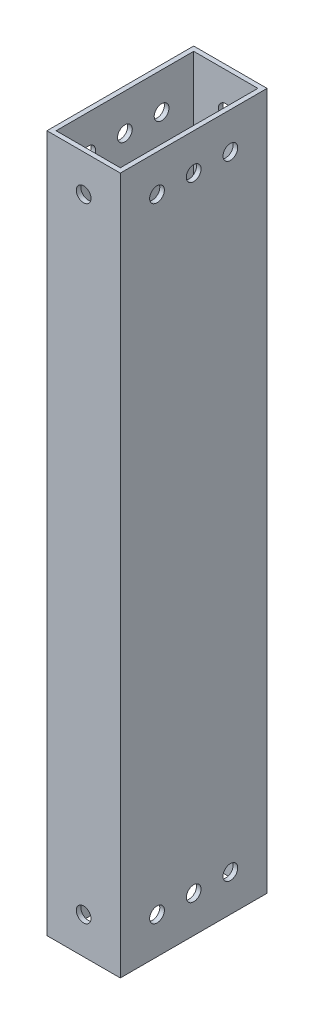
SolidWorks part; units mm, degrees
material "6061-T6 (SS)"
ref_plane "Front" through (0, 0, 0) normal (0, 0, 1) x (1, 0, 0)
ref_plane "Top" through (0, 0, 0) normal (0, 1, 0) x (1, 0, 0)
ref_plane "Right" through (0, 0, 0) normal (1, 0, 0) x (0, 0, -1)
sketch "Sketch1" plane through (0, 0, 0) normal (0, 1, 0) x (1, 0, 0)
  line L1 (12.7, 25.4) -> (-12.7, 25.4)
  line L2 (12.7, 25.4) -> (12.7, -25.4)
  line L3 (12.7, -25.4) -> (-12.7, -25.4)
  line L4 (-12.7, 25.4) -> (-12.7, -25.4)
  line L5 (12.7, 25.4) -> (-12.7, -25.4) construction
  line L6 (12.7, -25.4) -> (-12.7, 25.4) construction
  point P0 (0, 0)
  dimension "D1" = 25.4
  dimension "D2" = 50.8
extrude "Extrude-Thin1" add sketch "Sketch1" along normal up to surface (241.3 mm away) thin thin type one direction reverse wall 1.5875
sketch "Sketch4" plane through (-12.7, 0, 0) normal (-1, 0, 0) x (0, 0, 1)
  line L0 (-12.7, 12.7) -> (12.7, 12.7) construction
  line L3 (-12.7, 228.6) -> (12.7, 228.6) construction
  line L4 (-25.4, 0) -> (25.4, 0) construction
  line L5 (-25.4, 241.3) -> (25.4, 241.3) construction
  line L6 (-25.4, 241.3) -> (-25.4, 0) construction
  point P1 (-12.7, 12.7)
  point P2 (12.7, 12.7)
  point P6 (-12.7, 228.6)
  point P7 (12.7, 228.6)
  point P10 (0, 228.6)
  point P16 (-12.7, 228.6)
  point P18 (12.7, 228.6)
  point P22 (0, 12.7)
  point P26 (12.7, 12.7)
  point P28 (-12.7, 12.7)
  dimension "D1" = 12.7
  dimension "D2" = 12.7
  dimension "D3" = 12.7
hole_wizard "#10 Clearance Hole1" positions "Sketch4" profile "Sketch3" hole size "#10" standard "ANSI Inch" end condition through all
sketch "Sketch3" plane through (-12.7, 12.7, -12.7) normal (0, 1, 0) x (0, 0, 1)
  line L0 (0, 0) -> (0, 25.4)
  line L1 (0, 25.4) -> (2.5527, 25.4)
  line L2 (2.5527, 25.4) -> (2.5527, 0)
  line L5 (2.5527, 0) -> (0, 0)
  line L11 (0, -6.35) -> (0, 107.95) construction
  dimension "Thru Hole Dia." = 5.1054
  dimension "Thru Hole Depth" = 25.4
sketch "Sketch7" plane through (0, 0, 25.4) normal (0, 0, 1) x (1, 0, 0)
  line L0 (-12.7, 0) -> (12.7, 0) construction
  line L1 (-12.7, 241.3) -> (12.7, 241.3) construction
  point P0 (0, 12.7)
  point P2 (0, 228.6)
  dimension "D1" = 12.7
  dimension "D2" = 12.7
hole_wizard "#10 Clearance Hole2" positions "Sketch7" profile "Sketch6" hole size "#10" standard "ANSI Inch" end condition through all
sketch "Sketch6" plane through (0, 12.7, 25.4) normal (1, 0, 0) x (0, -1, 0)
  line L0 (0, 0) -> (0, 50.8)
  line L1 (0, 50.8) -> (2.5527, 50.8)
  line L2 (2.5527, 50.8) -> (2.5527, 0)
  line L5 (2.5527, 0) -> (0, 0)
  line L11 (0, -6.35) -> (0, 107.95) construction
  dimension "Thru Hole Dia." = 5.1054
  dimension "Thru Hole Depth" = 50.8
